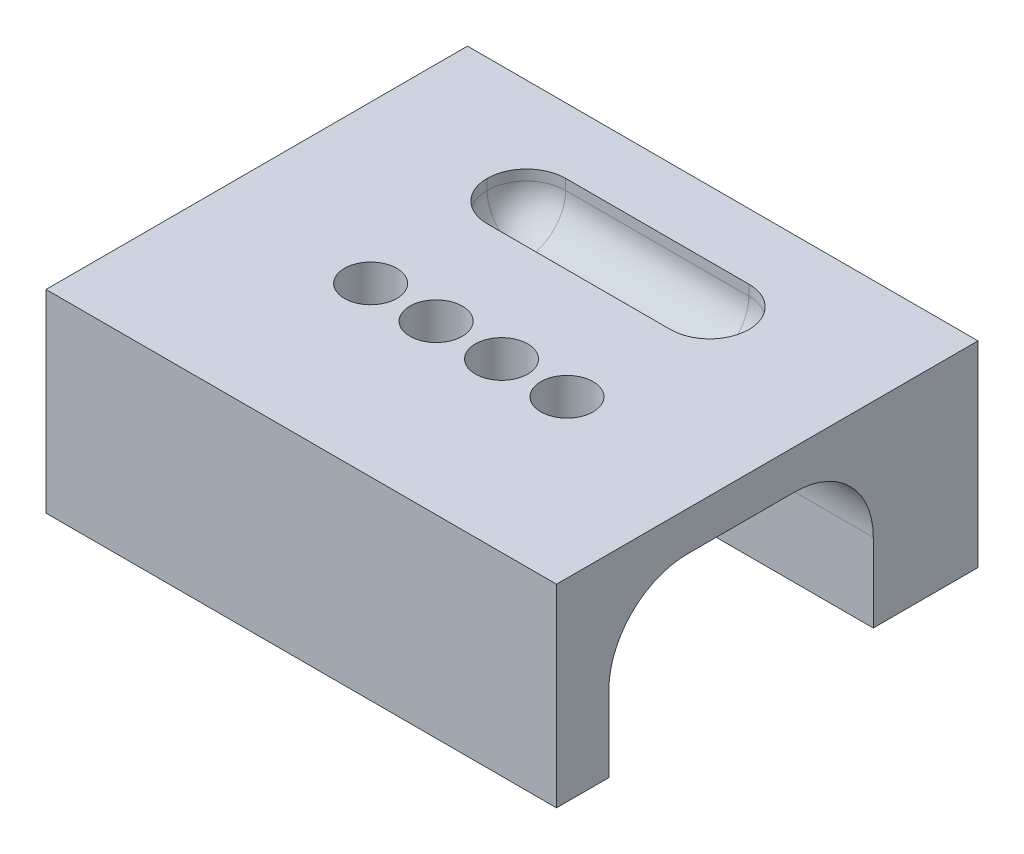
SolidWorks part; units mm, degrees
ref_plane "Front Plane" through (0, 0, 0) normal (0, 0, 1) x (1, 0, 0)
ref_plane "Top Plane" through (0, 0, 0) normal (0, 1, 0) x (1, 0, 0)
ref_plane "Right Plane" through (0, 0, 0) normal (1, 0, 0) x (0, 0, -1)
ref_plane "Plane3" through (0, 3.23, 0) normal (0, 1, 0) x (1, 0, 0)
sketch "Sketch21" plane through (0, 0, 0) normal (0, 1, 0) x (1, 0, 0)
  line L1 (-1.25, 12) -> (18.25, 12)
  line L2 (-1.25, 12) -> (-1.25, -12)
  line L3 (-1.25, -12) -> (18.25, -12)
  line L4 (18.25, 12) -> (18.25, -12)
  dimension "D1" = 18.25
  dimension "19.5" = 19.5
  dimension "D3" = 24
  dimension "D4" = 12
extrude "Boss-Extrude1" add sketch "Sketch21" along normal blind 4.44 and the other way blind 6
sketch "Sketch14" plane through (0, 3.23, 0) normal (0, 1, 0) x (1, 0, 0)
  circle A0 centre (4.75, 0) radius 1
  circle A1 centre (7.25, 0) radius 1
  circle A2 centre (9.75, 0) radius 1
  circle A3 centre (12.25, 0) radius 1
  dimension "D1" = 2.5
  dimension "D7" = 2
  dimension "D6" = 2
  dimension "D8" = 2
  dimension "D9" = 2
  dimension "D2" = 2.5
  dimension "D3" = 2.5
  dimension "D4" = 0
  dimension "D5" = 4.75
extrude "Cut-Extrude2" cut sketch "Sketch14" against normal through all both and the other way through all contours A0 | A1 | A2 | A3 region at (4.75, 3.23, 0) region at (7.25, 3.23, 0) region at (9.75, 3.23, 0) region at (12.25, 3.23, 0)
sketch "Sketch20" plane through (0, 0, 0) normal (1, 0, 0) x (0, 0, -1)
  line L0 (9.625, 3.23) -> (-9.625, 3.23) construction
  line L1 (-4.4, -0.36) -> (-4.4, -3.26)
  line L2 (-1.4, 2.64) -> (0, 2.64)
  line L6 (0, 2.64) -> (2.7, 2.64)
  line L19 (5.7, -0.36) -> (5.7, -3.36)
  line L24 (-16.1319, -7.1274) -> (15.5779, -7.1274)
  line L26 (9.7, -3.36) -> (5.7, -3.36)
  line L28 (-16.1319, 6.5474) -> (15.5779, 6.5474)
  line L30 (-6.4, 4.14) -> (9.7, 4.14)
  line L32 (-6.4, 4.14) -> (-6.4, -3.26)
  line L33 (9.7, 4.14) -> (9.7, -3.36)
  line L36 (-16.1319, 6.5474) -> (-16.1319, -7.1274)
  line L37 (15.5779, -7.1274) -> (15.5779, 6.5474)
  line L38 (-6.4, -3.26) -> (-4.4, -3.26)
  arc A0 (-1.4, 2.64) -> (-4.4, -0.36) centre (-1.4, -0.36) ccw
  arc A1 (2.7, 2.64) -> (5.7, -0.36) centre (2.7, -0.36) cw
  dimension "D3" = 3
  dimension "D4" = 3
  dimension "D1" = 1.4
  dimension "D2" = 0.59
  dimension "D5" = 6
  dimension "D6" = 0.91
  dimension "D7" = 2.7
  dimension "D8" = 0
  dimension "D10" = 2
  dimension "D11" = 4
extrude "Cut-Extrude4" cut sketch "Sketch20" against normal through all both and the other way through all
sketch "Sketch23" plane through (0, 4.14, 0) normal (0, 1, 0) x (1, 0, 0)
  line L0 (-1.25, 9.7) -> (18.25, 9.7) construction
  line L1 (-1.25, 5.7) -> (18.25, 5.7) construction
  line L2 (-1.25, 9.7) -> (18.25, 9.7) construction
  line L3 (3.5, 7.2) -> (13.5, 7.2)
  line L4 (3.5, 7.2) -> (3.5, 4.2)
  line L5 (3.5, 4.2) -> (13.5, 4.2)
  line L6 (13.5, 7.2) -> (13.5, 4.2)
  point P10 (8.5, 7.2)
  point P11 (8.5, 9.7)
  dimension "D1" = 4
  dimension "D2" = 5.5
  dimension "D3" = 3
  dimension "D4" = 10
  dimension "D5" = 0
extrude "Cut-Extrude5" cut sketch "Sketch23" against normal offset from surface (1.9 mm away) 0.4 up to face at (8.5, 2.64, -0.65) offset beyond the face yes
fillet "Fillet1" radius 1.5 2 edges at (8.5, 2.24, -7.2) (8.5, 2.24, -4.2)
fillet "Fillet2" radius 1.5 8 edges at (3.5, 3.94, -4.2) (3.5, 3.94, -7.2) (3.5, 2.6793, -6.7607) (13.5, 3.94, -7.2) (13.5, 3.94, -4.2) (13.5, 2.6793, -4.6393) (3.5, 2.6793, -4.6393) (13.5, 2.6793, -6.7607)
